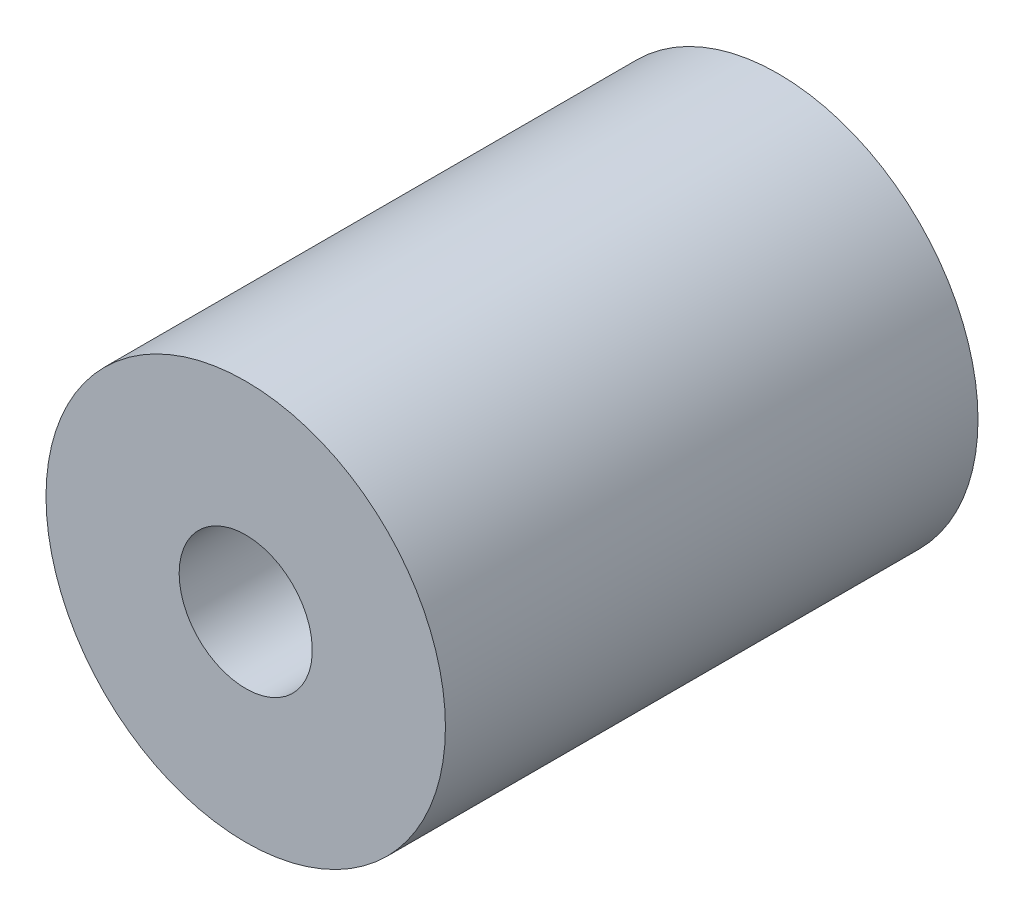
SolidWorks part; units mm, degrees
ref_plane "Front Plane" through (0, 0, 0) normal (0, 0, 1) x (1, 0, 0)
ref_plane "Top Plane" through (0, 0, 0) normal (0, 1, 0) x (1, 0, 0)
ref_plane "Right Plane" through (0, 0, 0) normal (1, 0, 0) x (0, 0, -1)
sketch "Sketch1" plane through (0, 0, 0) normal (1, 0, 0) x (0, 0, -1)
  line L0 (0, 0) -> (-12399.1975, 0) construction
  line L1 (0, 0) -> (0, 3.175) construction
  line L2 (0, 3.175) -> (0, 6.35)
  line L3 (0, 6.35) -> (12.7, 6.35)
  line L4 (12.7, 6.35) -> (12.7, 9.525)
  line L5 (12.7, 9.525) -> (-12.7, 9.525)
  line L6 (-12.7, 9.525) -> (-12.7, 3.175)
  line L7 (-12.7, 3.175) -> (0, 3.175)
  dimension "D1" = 3.175
  dimension "D2" = 6.35
  dimension "D3" = 9.525
  dimension "D4" = 25.4
  dimension "D5" = 12.7
revolve "Revolve1" add sketch "Sketch1" angle 360 about L0
sketch "Sketch2" plane through (0, 0, 0) normal (0, 1, 0) x (1, 0, 0)
  circle A0 centre (0, -6.35) radius 1.9685
  circle A1 centre (0, 6.35) radius 1.9685
  dimension "D1" = 3.937
  dimension "D2" = 6.35
  dimension "D3" = 6.35
extrude "Cut-Extrude1" cut sketch "Sketch2" against normal up to surface (9.525 mm away) up to face at (-9.525, 0, 12.7)
ref_axis "Axis1" through (0, -9.525, 6.35) along (0, 1, 0)
